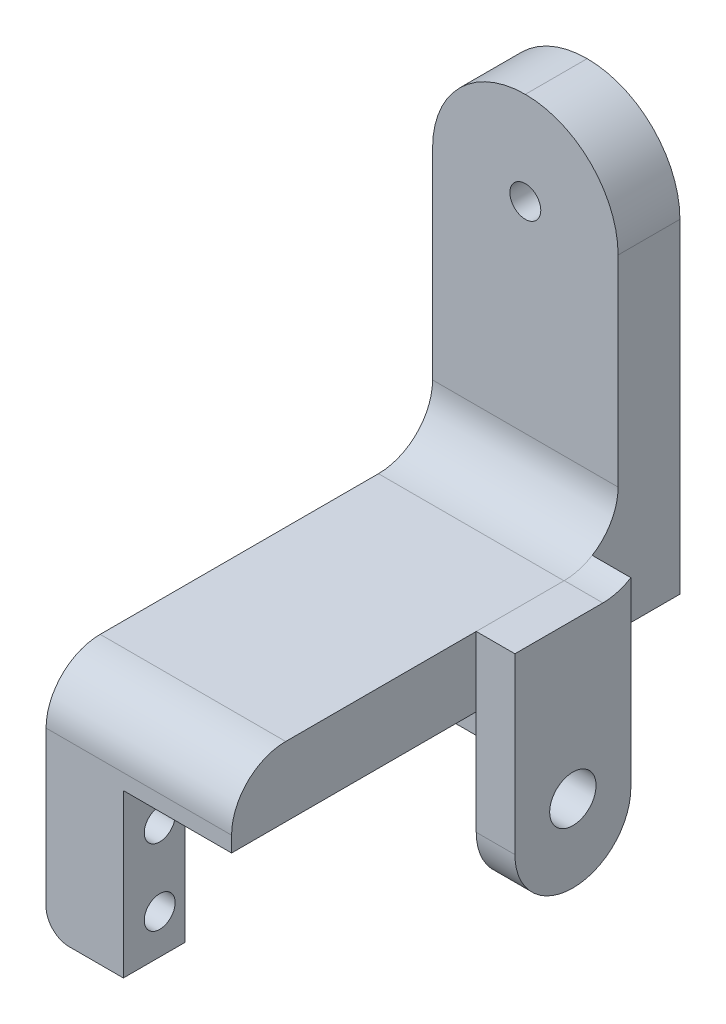
SolidWorks part; units mm, degrees
ref_plane "Front Plane" through (0, 0, 0) normal (0, 0, 1) x (1, 0, 0)
ref_plane "Top Plane" through (0, 0, 0) normal (0, 1, 0) x (1, 0, 0)
ref_plane "Right Plane" through (0, 0, 0) normal (1, 0, 0) x (0, 0, -1)
sketch "Sketch2" plane through (0, -0.0002, -27.9978) normal (0, 0, -1) x (1, 0, 0)
  line L1 (45.1952, -27.127) -> (69.1952, -27.127)
  line L2 (45.1952, -27.127) -> (45.1952, 47.873)
  line L3 (45.1952, 47.873) -> (69.1952, 47.873)
  line L4 (69.1952, -27.127) -> (69.1952, 47.873)
  dimension "D4" = 75
extrude "Boss-Extrude1" add sketch "Sketch2" along normal blind 8
fillet "Fillet1" radius 12 2 edges at (45.1952, 27.1268, -31.9981) (69.1952, 27.1268, -31.9981)
sketch "Sketch3" plane through (0, -0.0002, -27.9978) normal (0, 0, 1) x (1, 0, 0)
  line L0 (69.1952, 15.127) -> (69.1952, -47.873) construction
  line L1 (45.1952, -47.873) -> (69.1952, -47.873)
  line L2 (45.1952, -47.873) -> (45.1952, -17.873)
  line L3 (45.1952, -17.873) -> (69.1952, -17.873)
  line L4 (69.1952, -47.873) -> (69.1952, -17.873)
  dimension "D1" = 30
extrude "Boss-Extrude2" add sketch "Sketch3" along normal blind 50
sketch "Sketch4" plane through (69.1952, 0, 0) normal (1, 0, 0) x (0, 0, -1)
  line L2 (27.9977, -54.1007) -> (27.9977, -26.8732)
  line L3 (27.9977, -26.8732) -> (-14.0023, -26.8732)
  line L4 (-14.0023, -54.1007) -> (-14.0023, -26.8732)
  line L5 (-22.0023, -17.8728) -> (35.9977, -17.8728) construction
  line L6 (35.998, 15.1267) -> (35.9975, -47.8733) construction
  line L7 (6.9977, -17.8728) -> (6.9977, -54.1007) construction
  line L8 (27.9977, -54.1007) -> (-14.0023, -54.1007)
  dimension "D1" = 21
  dimension "D2" = 42
extrude "Cut-Extrude1" cut sketch "Sketch4" against normal up to surface (24 mm away) up to face at (45.1952, -16.8731, -13.9977)
fillet "Fillet2" radius 7 2 edges at (57.1952, -17.8728, 22.0023) (57.1952, -17.8732, -27.9977)
sketch "Sketch5" plane through (69.1952, 0, 0) normal (1, 0, 0) x (0, 0, -1)
  line L10 (-22.0025, -47.8728) -> (-22.0024, -24.8728) construction
  line L11 (35.998, 15.1267) -> (35.9975, -47.8733) construction
  line L20 (20.9977, -17.8732) -> (-15.0023, -17.8729)
  line L21 (-22.0024, -24.8728) -> (-22.0025, -47.8728)
  line L22 (-22.0025, -47.8728) -> (-14.0023, -47.8729)
  line L23 (-14.0023, -47.8729) -> (-14.0023, -26.8732)
  line L24 (-14.0023, -26.8732) -> (27.9977, -26.8732)
  line L25 (27.9977, -26.8732) -> (27.9977, -47.8732)
  line L26 (27.9977, -47.8732) -> (35.9975, -47.8733)
  line L27 (35.9975, -47.8733) -> (35.998, 15.1267)
  line L28 (35.998, 15.1267) -> (27.998, 15.1268)
  line L29 (27.998, 15.1268) -> (27.9978, -10.8732)
  line L31 (-22.0024, -26.8732) -> (-22.0025, -47.8728)
  line L32 (-22.0025, -47.8728) -> (35.9975, -47.8733)
  line L34 (-22.0024, -26.8732) -> (35.9976, -26.8732)
  line L37 (35.9975, -47.8733) -> (35.9976, -26.8732)
  arc A2 (-15.0023, -17.8729) -> (-22.0024, -24.8728) centre (-15.0024, -24.8729) ccw
  arc A3 (20.9977, -17.8732) -> (27.9978, -10.8732) centre (20.9978, -10.8732) ccw
  dimension "D1" = 0
extrude "Cut-Extrude3" cut sketch "Sketch5" against normal blind 14
sketch "Sketch6" plane through (69.1952, 0, 0) normal (1, 0, 0) x (0, 0, -1)
  line L0 (6.9976, -26.8732) -> (6.9976, -51.8245) construction
  line L1 (35.9976, -26.8732) -> (-22.0024, -26.8732) construction
  line L2 (1.5238, -51.8245) -> (14.5238, -51.8245) construction
  line L3 (-15.0023, -17.8729) -> (20.9977, -17.8732) construction
  line L4 (21.0341, -17.8731) -> (9.6476, -17.8731)
  line L5 (24.6476, -16.8463) -> (24.6476, -47.8732)
  line L6 (24.6476, -47.8732) -> (9.6476, -47.8731)
  line L7 (9.6476, -17.8731) -> (9.6476, -47.8731)
  line L8 (-13.0023, -47.8732) -> (26.9977, -47.8732) construction
  circle A0 centre (-3.1523, -37.8732) radius 3 construction
  circle A1 centre (17.1476, -37.8732) radius 3
  arc A2 (20.9977, -17.8732) -> (27.9978, -10.8732) centre (20.9978, -10.8732) ccw construction
  arc A3 (21.0341, -17.8731) -> (24.6476, -16.8463) centre (20.9978, -10.8732) ccw
  point P15 (24.6476, -47.8732)
  dimension "D4" = 30
extrude "Boss-Extrude3" add sketch "Sketch6" along normal blind 5
fillet "Fillet3" radius 3 2 edges at (45.1952, -47.8728, 18.0024) (45.1952, -47.8732, -31.9976)
sketch "Sketch7" plane through (0, -0.0002, -27.9978) normal (0, 0, 1) x (1, 0, 0)
  line L0 (57.1952, 27.127) -> (57.1952, 15.127) construction
  arc A0 (69.1952, 15.127) -> (57.1952, 27.127) centre (57.1952, 15.127) ccw construction
  arc A1 (69.1952, 15.127) -> (57.1952, 27.127) centre (57.1952, 15.127) ccw construction
  circle A2 centre (57.1952, 15.127) radius 2
extrude "Cut-Extrude4" cut sketch "Sketch7" against normal through all
sketch "Sketch8" plane through (0, -0.0003, -35.9978) normal (0, 0, -1) x (-1, 0, 0)
  circle A0 centre (-57.1952, 15.127) radius 3
extrude "Cut-Extrude5" cut sketch "Sketch8" against normal blind 4
sketch "Sketch9" plane through (55.1952, 0, 0) normal (1, 0, 0) x (0, 0, -1)
  circle A0 centre (31.2977, -42.7732) radius 2
  circle A1 centre (31.2977, -32.9732) radius 2
  circle A2 centre (-17.3023, -42.7732) radius 2
  circle A3 centre (-17.3023, -32.9732) radius 2
extrude "Cut-Extrude6" cut sketch "Sketch9" against normal blind 10
fillet "Fillet4" radius 7.5 2 edges at (71.6952, -47.8732, -24.6476) (71.6952, -47.8731, -9.6476)
